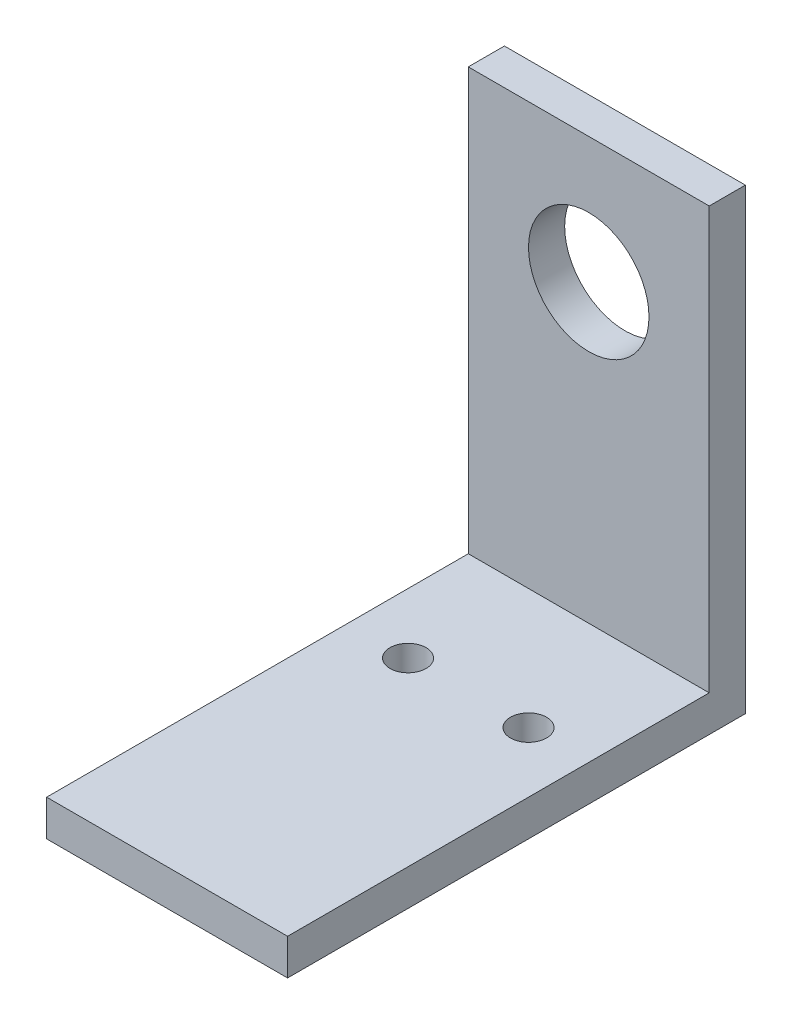
SolidWorks part; units mm, degrees
ref_plane "前视基准面" through (0, 0, 0) normal (0, 0, 1) x (1, 0, 0)
ref_plane "上视基准面" through (0, 0, 0) normal (0, 1, 0) x (1, 0, 0)
ref_plane "右视基准面" through (0, 0, 0) normal (1, 0, 0) x (0, 0, -1)
sketch "草图1" plane through (0, 0, 0) normal (0, 0, 1) x (1, 0, 0)
  line L1 (-10, 19) -> (10, 19)
  line L2 (-10, 19) -> (-10, -19)
  line L3 (-10, -19) -> (10, -19)
  line L4 (10, 19) -> (10, -19)
  line L5 (-10, 19) -> (10, -19) construction
  line L6 (-10, -19) -> (10, 19) construction
  point P0 (0, 0)
  dimension "D1" = 20
  dimension "D2" = 38
extrude "凸台-拉伸1" add sketch "草图1" along normal blind 3
sketch "草图2" plane through (0, 0, 3) normal (0, 0, 1) x (1, 0, 0)
  line L0 (10, -19) -> (10, 19) construction
  line L1 (-10, -19) -> (10, -19)
  line L2 (-10, -19) -> (-10, -16)
  line L3 (-10, -16) -> (10, -16)
  line L4 (10, -19) -> (10, -16)
  dimension "D1" = 3
extrude "凸台-拉伸2" add sketch "草图2" along normal blind 35
sketch "草图3" plane through (0, 0, 0) normal (0, 0, -1) x (-1, 0, 0)
  line L1 (10, -19) -> (-10, -19) construction
  circle A0 centre (0, 8.53) radius 5
  dimension "D1" = 10
  dimension "D2" = 27.53
sketch "草图4" plane through (0, -16, 0) normal (0, 1, 0) x (1, 0, 0)
  line L0 (-10, -38) -> (-10, -3) construction
  line L1 (10, -38) -> (10, -3) construction
  line L2 (10, -38) -> (-10, -38) construction
  circle A0 centre (-5, -13) radius 1.5
  circle A1 centre (5, -13) radius 1.5
  dimension "D1" = 5
  dimension "D2" = 5
  dimension "D3" = 3
  dimension "D4" = 3
  dimension "D5" = 25
  dimension "D6" = 25
extrude "切除-拉伸2" cut sketch "草图4" against normal blind 10
sketch "草图6" plane through (0, 0, 0) normal (0, 0, -1) x (-1, 0, 0)
  circle A0 centre (0, 8.53) radius 5
extrude "切除-拉伸4" cut sketch "草图6" against normal blind 10
